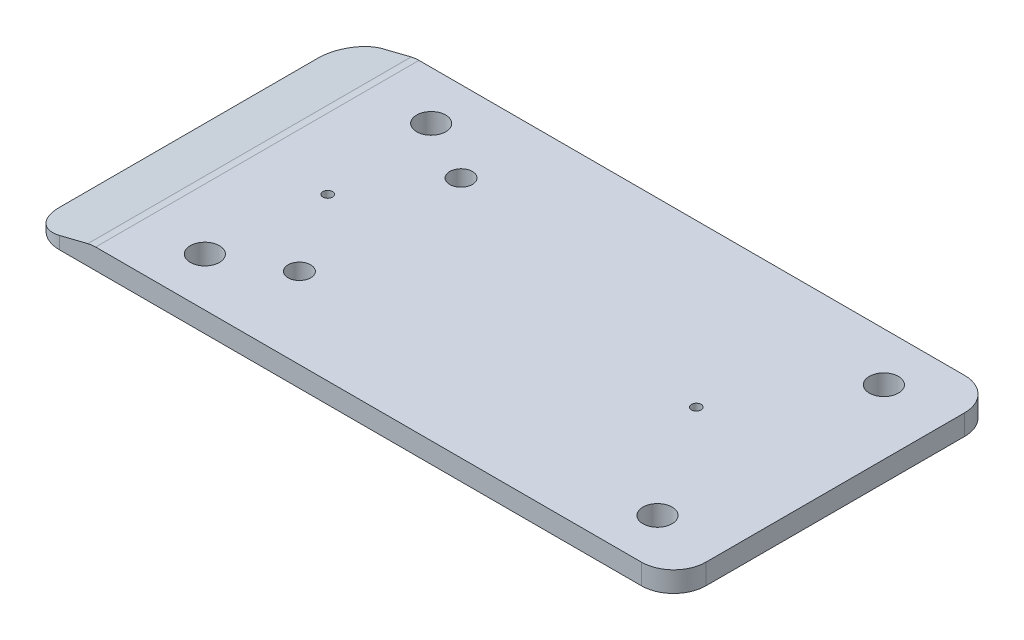
SolidWorks part; units mm, degrees
ref_plane "Front Plane" through (0, 0, 0) normal (0, 0, 1) x (1, 0, 0)
ref_plane "Top Plane" through (0, 0, 0) normal (0, 1, 0) x (1, 0, 0)
ref_plane "Right Plane" through (0, 0, 0) normal (1, 0, 0) x (0, 0, -1)
sketch "Sketch1" plane through (0, 0, 0) normal (0, 1, 0) x (1, 0, 0)
  line L1 (-100, -50) -> (100, -50)
  line L2 (-100, -50) -> (-100, 50)
  line L3 (-100, 50) -> (100, 50)
  line L4 (100, -50) -> (100, 50)
  line L5 (-100, -50) -> (100, 50) construction
  line L6 (-100, 50) -> (100, -50) construction
  point P0 (0, 0)
  dimension "D1" = 200
  dimension "D2" = 100
extrude "Boss-Extrude1" add sketch "Sketch1" along normal blind 6.35
chamfer "Chamfer1" distance 5 distance2 20 1 edges at (-100, 6.35, 0) first distance on face at (-100, 3.175, 0)
fillet "Fillet1" radius 10 5 edges at (-100, 0.675, -50) (100, 3.175, -50) (100, 3.175, 50) (-100, 0.675, 50) (-80, 6.35, 0)
hole_wizard "Ø3.0mm Dowel Hole1" positions "Sketch2" profile "Sketch4" hole size "Ø3.0" standard "ANSI Metric" end condition through all
sketch "Sketch2" plane through (0, 6.35, 0) normal (0, 1, 0) x (1, 0, 0)
  line L2 (0, 0) -> (57, 0) construction
  line L4 (0, 0) -> (-57, 0) construction
  point P8 (57, 0)
  point P13 (-57, 0)
  dimension "D1" = 114
sketch "Sketch4" plane through (-57, 6.35, 0) normal (1, 0, 0) x (0, 0, 1)
  line L0 (0, 0) -> (0, 6.35)
  line L1 (0, 6.35) -> (1.5, 6.35)
  line L2 (1.5, 6.35) -> (1.5, 0)
  line L5 (1.5, 0) -> (0, 0)
  line L11 (0, -6.35) -> (0, 107.95) construction
  dimension "Thru Hole Dia." = 3
  dimension "Thru Hole Depth" = 6.35
hole_wizard "M8 Clearance Hole1" positions "Sketch5" profile "Sketch6" hole size "M8" standard "ANSI Metric" end condition through all
sketch "Sketch5" plane through (0, 6.35, 0) normal (0, 1, 0) x (1, 0, 0)
  line L2 (-60, 35) -> (80, 35)
  line L3 (-60, 35) -> (-60, -35)
  line L4 (-60, -35) -> (80, -35)
  line L5 (80, 35) -> (80, -35)
  line L6 (100, -40) -> (100, 40) construction
  point P247 (-60, 35)
  point P248 (80, -35)
  point P409 (-60, -35)
  point P410 (80, 35)
  point P412 (-60, 0)
  dimension "D1" = 70
  dimension "D2" = 140
  dimension "D3" = 20
sketch "Sketch6" plane through (-60, 6.35, -35) normal (1, 0, 0) x (0, 0, 1)
  line L0 (0, 0) -> (0, 6.35)
  line L1 (0, 6.35) -> (4.5, 6.35)
  line L2 (4.5, 6.35) -> (4.5, 0)
  line L5 (4.5, 0) -> (0, 0)
  line L11 (0, -6.35) -> (0, 107.95) construction
  dimension "Thru Hole Dia." = 9
  dimension "Thru Hole Depth" = 6.35
hole_wizard "Ø6.0mm Dowel Hole1" positions "Sketch7" profile "Sketch8" hole size "Ø6.0" standard "ANSI Metric" end condition through all
sketch "Sketch7" plane through (0, 6.35, 0) normal (0, 1, 0) x (1, 0, 0)
  line L0 (-40.7689, 25) -> (-40.7689, -25) construction
  line L2 (-78.7689, 50) -> (-78.7689, -50) construction
  point P0 (-40.7689, 25)
  point P2 (-40.7689, -25)
  point P9 (-40.7689, 0)
  dimension "D1" = 38
  dimension "D2" = 50
sketch "Sketch8" plane through (-40.7689, 6.35, -25) normal (1, 0, 0) x (0, 0, 1)
  line L0 (0, 0) -> (0, 6.35)
  line L1 (0, 6.35) -> (3.5, 6.35)
  line L2 (3.5, 6.35) -> (3.5, 0)
  line L5 (3.5, 0) -> (0, 0)
  line L11 (0, -6.35) -> (0, 107.95) construction
  dimension "Thru Hole Dia." = 7
  dimension "Thru Hole Depth" = 6.35
